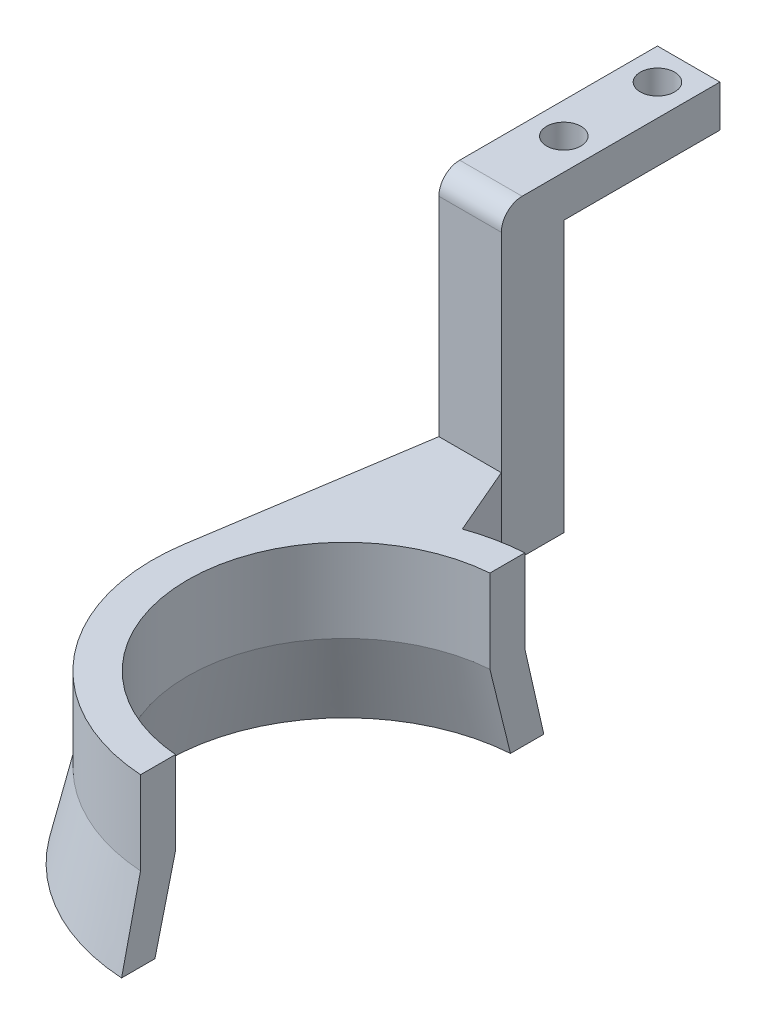
SolidWorks part; units mm, degrees
ref_plane "前视基准面" through (0, 0, 0) normal (0, 0, 1) x (1, 0, 0)
ref_plane "上视基准面" through (0, 0, 0) normal (0, 1, 0) x (1, 0, 0)
ref_plane "右视基准面" through (0, 0, 0) normal (1, 0, 0) x (0, 0, -1)
other "Configuration Table"
sketch "草图1" plane through (0, 0, 0) normal (0, 1, 0) x (1, 0, 0)
  line L1 (0, 0) -> (6, 0)
  line L2 (0, 0) -> (0, -15)
  line L3 (0, -15) -> (6, -15)
  line L4 (6, 0) -> (6, -15)
  circle A0 centre (3, -3) radius 1.65
  circle A1 centre (3, -12) radius 1.65
  point P9 (3, 0)
  dimension "D3" = 3.3
  dimension "D4" = 3.3
  dimension "D1" = 6
  dimension "D2" = 15
  dimension "D5" = 9
  dimension "D6" = 3
extrude "凸台-拉伸1" add sketch "草图1" along normal blind 2
sketch "草图2" plane through (6, 0, 0) normal (1, 0, 0) x (0, 0, -1)
  line L0 (-15, 0) -> (0, 0) construction
  line L1 (-15, 2) -> (-19, 2)
  line L2 (-15, 2) -> (-15, -20)
  line L3 (-15, -20) -> (-21, -20)
  line L4 (-21, 0) -> (-21, -20)
  arc A0 (-19, 2) -> (-21, 0) centre (-19, 0) ccw
  point P9 (-21, 2)
  dimension "D3" = 2
  dimension "D1" = 20
  dimension "D2" = 6
extrude "凸台-拉伸2" add sketch "草图2" against normal blind 6
sketch "草图3" plane through (0, -20, 0) normal (0, -1, 0) x (1, 0, 0)
  line L1 (0, 15) -> (6, 15)
  line L2 (0, 15) -> (0, 45)
  line L3 (0, 45) -> (6, 45)
  line L4 (6, 15) -> (6, 45)
  dimension "D1" = 6
  dimension "D2" = 30
extrude "凸台-拉伸3" add sketch "草图3" along normal blind 8
sketch "草图5" plane through (0, -20, 0) normal (0, 1, 0) x (1, 0, 0)
  line L0 (6, -21) -> (6, -45) construction
  line L1 (6, -45) -> (0, -45) construction
  line L2 (13.8, -26.539) -> (13.8, -63.461)
  line L3 (6, -21) -> (8.8162, -27.5641)
  line L5 (0, -21) -> (-3.0242, -40.5055)
  arc A0 (13.8, -26.539) -> (13.8, -63.461) centre (15, -45) ccw
  line M4 (6, -45) -> (6, -21)
  dimension "D2" = 18.5
  dimension "D1" = 9
  dimension "D3" = 7.8
extrude "凸台-拉伸4" add sketch "草图5" against normal blind 8 contours A0 M4 | L2 A0 region at (6.496, -20, 45) region at (6.9331, -20, 25.7712)
sketch "草图7" plane through (0, -20, 0) normal (0, 1, 0) x (1, 0, 0)
  line L0 (13.8, -26.539) -> (13.8, -63.461) construction
  line L1 (13.8, -29.8976) -> (13.8, -60.1024)
  arc A0 (13.8, -29.8976) -> (13.8, -60.1024) centre (15, -45) ccw
  dimension "D1" = 15.15
extrude "切除-拉伸1" cut sketch "草图7" against normal up to next
sketch "草图8" plane through (0, -20, 0) normal (0, 1, 0) x (1, 0, 0)
  line L0 (0, -21) -> (-3.2957, -42.2582)
  line L1 (-3.2957, -42.2582) -> (2.1434, -32.7021)
  line L2 (2.1434, -32.7021) -> (0, -21)
  arc A0 (0, -34.1718) -> (13.8, -63.461) centre (15, -45) ccw construction
extrude "凸台-拉伸5" add sketch "草图8" against normal blind 8
ref_plane "基准面1" through (0, -36, 0) normal (0, -1, 0) x (-1, 0, 0)
sketch "草图9" plane through (0, -36, 0) normal (0, -1, 0) x (-1, 0, 0)
  line L0 (-13.8, -60.1024) -> (-13.8, -63.461) construction
  line L1 (-13.8, -26.539) -> (-13.8, -29.8976) construction
  line L2 (-13.8, -24.7155) -> (-13.8, -27.9221)
  line L3 (-13.8, -62.0779) -> (-13.8, -65.2845)
  arc A0 (-13.8, -27.9221) -> (-13.8, -62.0779) centre (-15, -45) cw
  arc A4 (-13.8, -24.7155) -> (-13.8, -65.2845) centre (-15, -45) cw
  point P10 (-15, -45)
  dimension "D1" = 17.12
  dimension "D2" = 20.32
sketch "草图10" plane through (0, -28, 0) normal (0, -1, 0) x (1, 0, 0)
  line L0 (13.8, 24.7155) -> (13.8, 27.9221) construction
  line L1 (13.8, 63.461) -> (13.8, 60.1024)
  line L2 (13.8, 29.8976) -> (13.8, 26.539)
  arc A0 (13.8, 60.1024) -> (13.8, 29.8976) centre (15, 45) ccw
  arc A1 (13.8, 60.1024) -> (13.8, 29.8976) centre (15, 45) ccw construction
  arc A2 (13.8, 63.461) -> (13.8, 26.539) centre (15, 45) ccw
loft "放样1" add profiles "草图10", "草图9" connector at (13.8, -28, 60.1024) connector at (13.8, -36, 62.0779)
ref_plane "基准面2" through (28, 0, 0) normal (1, 0, 0) x (0, 0, -1)
sketch "草图11" plane through (0, 0, 0) normal (0, -1, 0) x (1, 0, 0)
  line L1 (0, 15) -> (6, 15)
  line L2 (0, 15) -> (0, 0)
  line L3 (0, 0) -> (6, 0)
  line L4 (6, 15) -> (6, 0)
  circle A0 centre (3, 12) radius 1.65
  circle A1 centre (3, 3) radius 1.65
extrude "凸台-拉伸6" add sketch "草图11" along normal blind 2
